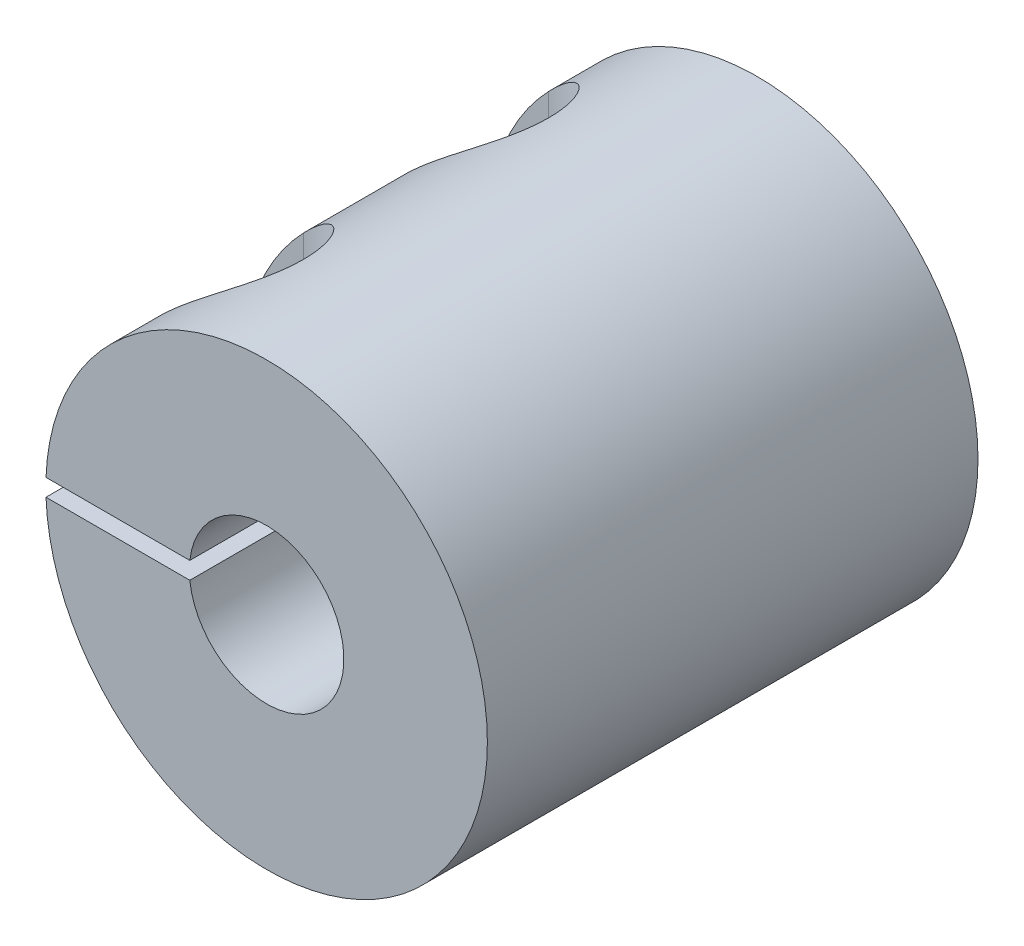
SolidWorks part; units mm, degrees
ref_plane "Спереди" through (0, 0, 0) normal (0, 0, 1) x (1, 0, 0)
ref_plane "Сверху" through (0, 0, 0) normal (0, 1, 0) x (1, 0, 0)
ref_plane "Справа" through (0, 0, 0) normal (1, 0, 0) x (0, 0, -1)
sketch "Эскиз1" plane through (0, 0, 0) normal (0, 0, 1) x (1, 0, 0)
  circle A0 centre (0, 0) radius 9
  dimension "D1" = 18
extrude "Бобышка-Вытянуть1" add sketch "Эскиз1" along normal blind 20
sketch "Эскиз2" plane through (0, 0, 20) normal (0, 0, 1) x (1, 0, 0)
  circle A0 centre (0, 0) radius 3.15
  dimension "D1" = 6.3
extrude "Вырез-Вытянуть1" cut sketch "Эскиз2" against normal through all
sketch "Эскиз3" plane through (0, 0, 0) normal (0, 0, -1) x (-1, 0, 0)
  circle A0 centre (0, 0) radius 4
  dimension "D1" = 8
extrude "Вырез-Вытянуть2" cut sketch "Эскиз3" against normal blind 10
sketch "Эскиз4" plane through (0, 0, 0) normal (0, 0, -1) x (-1, 0, 0)
  line L1 (2.2939, 0.35) -> (13.428, 0.35)
  line L2 (2.2939, 0.35) -> (2.2939, -0.35)
  line L3 (2.2939, -0.35) -> (13.428, -0.35)
  line L4 (13.428, 0.35) -> (13.428, -0.35)
  point P4 (2.2939, 0)
  dimension "D1" = 0
  dimension "D2" = 0.7
extrude "Вырез-Вытянуть3" cut sketch "Эскиз4" against normal through all
ref_plane "Плоскость1" through (0, 2.85, 0) normal (0, -1, 0) x (-1, 0, 0)
sketch "Эскиз5" plane through (0, 2.85, 0) normal (0, -1, 0) x (-1, 0, 0)
  line L0 (8.9932, 0) -> (-9, 0) construction
  line L1 (-9, -20) -> (8.9932, -20) construction
  line L3 (6.5, -2) -> (11.7803, -2)
  line L4 (11.7803, -2) -> (11.7803, -8)
  line L5 (11.7803, -8) -> (6.5, -8)
  line L6 (6.5, -12) -> (11.7803, -12)
  line L7 (6.5, -18) -> (11.7803, -18)
  line L8 (11.7803, -18) -> (11.7803, -12)
  arc A0 (6.5, -2) -> (6.5, -8) centre (6.5, -5) ccw
  arc A1 (6.5, -12) -> (6.5, -18) centre (6.5, -15) ccw
  dimension "D1" = 6
  dimension "D2" = 5
  dimension "D3" = 5
  dimension "D4" = 6.5
extrude "Вырез-Вытянуть4" cut sketch "Эскиз5" against normal through all
sketch "Эскиз6" plane through (0, 2.85, 0) normal (0, 1, 0) x (1, 0, 0)
  circle A0 centre (-6.5, -5) radius 1.5
  circle A1 centre (-6.5, -15) radius 1.5
  dimension "D1" = 3
extrude "Вырез-Вытянуть5" cut sketch "Эскиз6" against normal up to surface (2.5 mm away) up to face at (-5.3694, 0.35, 10)
sketch "Эскиз7" plane through (0, -0.35, 0) normal (0, 1, 0) x (1, 0, 0)
  circle A0 centre (-6.5, -5) radius 1.25
  circle A1 centre (-6.5, -15) radius 1.25
  dimension "D1" = 2.5
extrude "Вырез-Вытянуть6" cut sketch "Эскиз7" against normal through all
